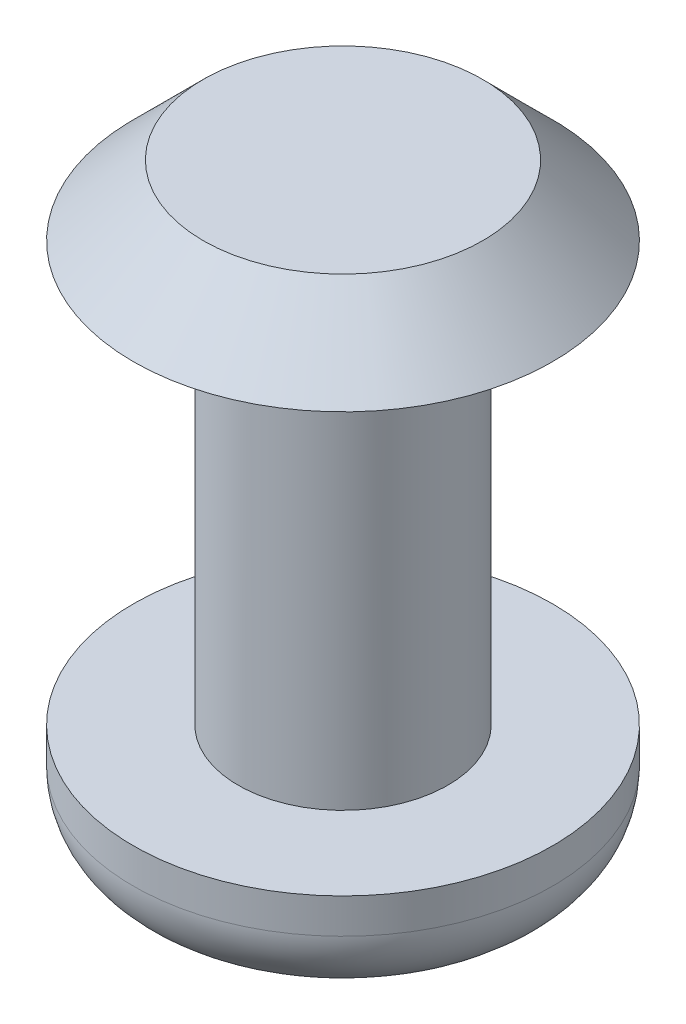
SolidWorks part; units mm, degrees
ref_plane "Plan de face" through (0, 0, 0) normal (0, 0, 1) x (1, 0, 0)
ref_plane "Plan de dessus" through (0, 0, 0) normal (0, 1, 0) x (1, 0, 0)
ref_plane "Plan de droite" through (0, 0, 0) normal (1, 0, 0) x (0, 0, -1)
sketch "Esquisse1" plane through (0, 0, 0) normal (0, 0, 1) x (1, 0, 0)
  line L0 (0, 0) -> (0, 6)
  dimension "D1" = 6
revolve "Révol.-Mince1" add sketch "Esquisse1" angle 360 about L0 wall 1.5
sketch "Esquisse2" plane through (0, 6, 0) normal (0, 1, 0) x (1, 0, 0)
  circle A0 centre (0, 0) radius 3
  dimension "D1" = 6
extrude "Boss.-Extru.1" add sketch "Esquisse2" along normal blind 1 contours A0
chamfer "Chanfrein1" distance 1 angle 45 1 edges at (0, 7, 3)
sketch "Esquisse3" plane through (0, 0, 0) normal (0, -1, 0) x (1, 0, 0)
  circle A0 centre (0, 0) radius 3
  dimension "D1" = 6
extrude "Boss.-Extru.2" add sketch "Esquisse3" along normal blind 1.5 contours A0
fillet "Congé1" radius 1 1 edges at (0, -1.5, -3)
sketch "Esquisse4" plane through (0, -1.5, 0) normal (0, -1, 0) x (-1, 0, 0)
  circle A0 centre (0, 0) radius 1.25
  dimension "D1" = 2.5
extrude "Enlèv. mat.-Extru.1" cut sketch "Esquisse4" against normal blind 8
